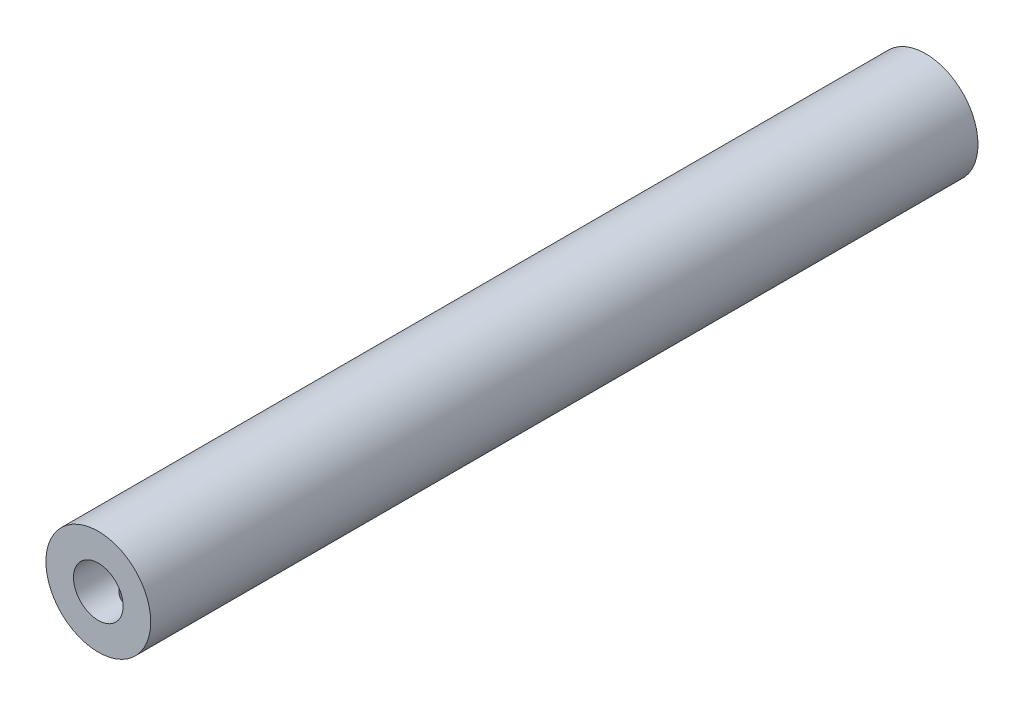
SolidWorks part; units mm, degrees
ref_plane "Front Plane" through (0, 0, 0) normal (0, 0, 1) x (1, 0, 0)
ref_plane "Top Plane" through (0, 0, 0) normal (0, 1, 0) x (1, 0, 0)
ref_plane "Right Plane" through (0, 0, 0) normal (1, 0, 0) x (0, 0, -1)
sketch "Sketch1" plane through (0, 0, 0) normal (0, 0, 1) x (1, 0, 0)
  circle A0 centre (0, 0) radius 4.75
  dimension "D1" = 9.5
extrude "Boss-Extrude1" add sketch "Sketch1" along normal blind 75
sketch "Sketch2" plane through (0, 0, 75) normal (0, 0, 1) x (1, 0, 0)
  circle A0 centre (0, 0) radius 2.25
  dimension "D1" = 4.5
extrude "Cut-Extrude1" cut sketch "Sketch2" against normal blind 12
sketch "Sketch3" plane through (0, 0, 0) normal (0, 1, 0) x (1, 0, 0)
  line L0 (0, -75) -> (0, -71) construction
  line L1 (-4.75, -75) -> (4.75, -75) construction
  circle A0 centre (0, -71) radius 1.5
  dimension "D1" = 3
  dimension "D2" = 4
extrude "Cut-Extrude2" cut sketch "Sketch3" against normal through all
